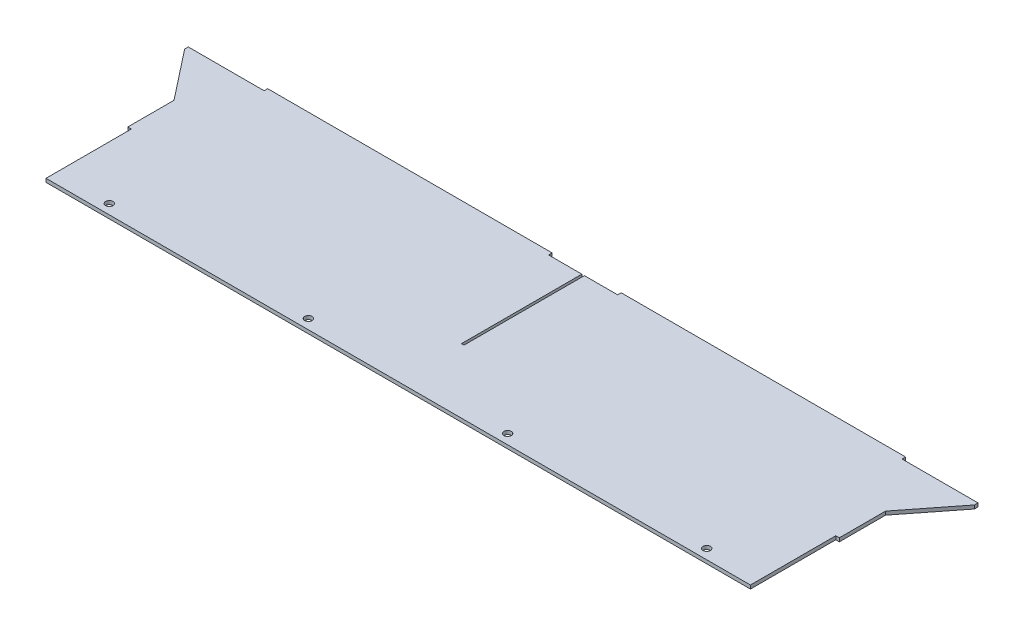
SolidWorks part; units mm, degrees
material "6061-T6 (SS)"
ref_plane "X-Y Datum" through (0, 0, 0) normal (0, 0, 1) x (1, 0, 0)
ref_plane "X-Z Datum" through (0, 0, 0) normal (0, 1, 0) x (1, 0, 0)
ref_plane "Y-Z Datum" through (0, 0, 0) normal (1, 0, 0) x (0, 0, -1)
sketch "Sketch1" plane through (0, 0, 0) normal (0, 1, 0) x (1, 0, 0)
  line L1 (-317.6778, 82.55) -> (317.6778, 82.55)
  line L2 (-317.6778, 82.55) -> (-317.6778, -82.55)
  line L3 (-317.6778, -82.55) -> (317.6778, -82.55)
  line L4 (317.6778, 82.55) -> (317.6778, -82.55)
  line L5 (-317.6778, 82.55) -> (317.6778, -82.55) construction
  line L6 (-317.6778, -82.55) -> (317.6778, 82.55) construction
  point P0 (0, 0)
  dimension "D1" = 635.3556
  dimension "D2" = 165.1
extrude "Boss-Extrude1" add sketch "Sketch1" along normal mid plane 3.175
sketch "Sketch2" plane through (0, 0, -82.55) normal (0, 0, -1) x (-1, 0, 0)
  line L20 (-317.6778, -1.5875) -> (317.6778, -1.5875) construction
  line L21 (-284.8229, -1.5875) -> (-30.8229, -1.5875)
  line L22 (30.8229, -1.5875) -> (284.8229, -1.5875)
  line L40 (30.8229, -1.5875) -> (30.8229, 1.5875)
  line L41 (30.8229, 1.5875) -> (284.8229, 1.5875)
  line L42 (284.8229, 1.5875) -> (284.8229, -1.5875)
  line L56 (-284.8229, -1.5875) -> (-284.8229, 1.5875)
  line L57 (-284.8229, 1.5875) -> (-30.8229, 1.5875)
  line L58 (-30.8229, 1.5875) -> (-30.8229, -1.5875)
extrude "Boss-Extrude2" add sketch "Sketch2" along normal blind 3.175
sketch "Sketch3" plane through (0, -1.5875, 0) normal (0, -1, 0) x (1, 0, 0)
  line L0 (317.6778, -82.55) -> (352.6028, -82.55)
  line L1 (352.6028, -82.55) -> (352.6028, -79.375)
  line L3 (352.6028, -79.375) -> (317.6778, -34.925)
  line L4 (317.6778, 82.55) -> (317.6778, -82.55) construction
  line L17 (317.6778, -82.55) -> (317.6778, 82.55)
  line L18 (317.6778, 82.55) -> (-317.6778, 82.55)
  line L19 (-317.6778, 82.55) -> (-317.6778, -82.55)
  line L20 (-317.6778, -82.55) -> (-284.8229, -82.55)
  line L21 (-284.8229, -82.55) -> (-284.8229, -85.725)
  line L22 (-284.8229, -85.725) -> (-30.8229, -85.725)
  line L23 (-30.8229, -85.725) -> (-30.8229, -82.55)
  line L24 (-30.8229, -82.55) -> (30.8229, -82.55)
  line L25 (30.8229, -82.55) -> (30.8229, -85.725)
  line L26 (30.8229, -85.725) -> (284.8229, -85.725)
  line L27 (284.8229, -85.725) -> (284.8229, -82.55)
  line L28 (284.8229, -82.55) -> (317.6778, -82.55)
  line L29 (317.6778, -82.55) -> (317.6778, -34.925)
  dimension "D1" = 34.925
  dimension "D2" = 3.175
  dimension "D3" = 44.45
  dimension "D4" = 0
extrude "Boss-Extrude3" add sketch "Sketch3" against normal blind 3.175
mirror "Mirror1" about plane through (0, 0, 0) normal (1, 0, 0) of "Boss-Extrude3"
sketch "Sketch4" plane through (0, -1.5875, 0) normal (0, -1, 0) x (1, 0, 0)
  line L0 (-284.4038, 82.55) -> (-284.4038, 71.882)
  line L1 (-317.6778, 82.55) -> (317.6778, 82.55) construction
  line L2 (-284.4038, 71.882) -> (-317.6778, 71.882)
  line L3 (-317.6778, -34.925) -> (-317.6778, 82.55) construction
  circle A0 centre (-284.4038, 71.882) radius 3.675
extrude "Cut-Extrude1" [suppressed] cut sketch "Sketch4" against normal through all contours L2 A0 L0 | L0 A0 L2
pattern_linear "LPattern1" [suppressed] count 5 spacing 139.7 of bodies 107
sketch "Sketch5" plane through (0, -1.5875, 0) normal (0, -1, 0) x (1, 0, 0)
  line L0 (-317.6778, 82.55) -> (317.6778, 82.55) construction
  line L1 (-317.6778, -34.925) -> (-317.6778, 82.55) construction
  line L2 (-317.6778, 82.55) -> (317.6778, 82.55)
  line L3 (-317.6778, -34.925) -> (-317.6778, 82.55)
  line L4 (0, 127.4245) -> (0, -127.4245) construction
  line L5 (-317.6778, 82.55) -> (-314.5028, 82.55)
  line L6 (-317.6778, 82.55) -> (-317.6778, 6.35)
  line L7 (-317.6778, 6.35) -> (-314.5028, 6.35)
  line L8 (-314.5028, 82.55) -> (-314.5028, 6.35)
  line L9 (317.6778, 6.35) -> (314.5028, 6.35)
  line L10 (314.5028, 82.55) -> (314.5028, 6.35)
  line L11 (317.6778, -34.925) -> (317.6778, 82.55)
  line L12 (30.8229, -82.55) -> (-30.8229, -82.55) construction
  line L13 (30.8229, -82.55) -> (-30.8229, -82.55)
  line L14 (-1.143, -85.725) -> (-1.143, -82.55) construction
  line L15 (-1.143, -85.725) -> (-1.143, -82.55)
  line L17 (-1.143, -82.55) -> (1.143, -82.55)
  line L18 (-1.143, -82.55) -> (-1.143, 24.892)
  line L19 (-1.143, 24.892) -> (1.143, 24.892)
  line L20 (1.143, -82.55) -> (1.143, 24.892)
  point P10 (0, 0)
  line M10 (317.6778, -34.925) -> (317.6778, 82.55)
  line M11 (317.6778, 82.55) -> (-317.6778, 82.55)
  line M12 (-317.6778, 82.55) -> (-317.6778, -34.925)
  dimension "D1" = 3.175
  dimension "D2" = 76.2
  dimension "D3" = 2.286
  dimension "D4" = 107.442
extrude "Cut-Extrude2" cut sketch "Sketch5" against normal through all contours L19 L4 L17 L20 | L4 L19 L18 L13 | L8 L2 L7 M12 | L10 L9 M11 M10 region at (316.0903, -1.5875, 44.45) region at (0.5715, -1.5875, -28.829) region at (-0.5715, -1.5875, -28.829) region at (-316.0903, -1.5875, 44.45)
sketch "Sketch6" plane through (0, -1.5875, 0) normal (0, -1, 0) x (1, 0, 0)
  line L0 (-314.5028, 82.55) -> (314.5028, 82.55) construction
  line L1 (-314.5028, 82.55) -> (314.5028, 82.55)
  line L2 (0, 127.6954) -> (0, 37.4046) construction
  line L3 (314.5028, 82.55) -> (314.5028, 6.35) construction
  circle A0 centre (266.7, 73.8124) radius 3
  point P6 (0, 82.55)
  dimension "D1" = 6
  dimension "D2" = 8.7376
  dimension "D3" = 47.8028
hole_wizard "M6 Clearance Hole1" positions "Sketch7" profile "Sketch8" hole size "M6" standard "ANSI Metric" end condition through all
sketch "Sketch7" plane through (0, 1.5875, 0) normal (0, 1, 0) x (1, 0, 0)
  point P0 (266.7, -73.8124)
sketch "Sketch8" plane through (266.7, 1.5875, 73.8124) normal (1, 0, 0) x (0, 0, 1)
  line L0 (0, 0) -> (0, 3.175)
  line L1 (0, 3.175) -> (3.3, 3.175)
  line L2 (3.3, 3.175) -> (3.3, 0)
  line L5 (3.3, 0) -> (0, 0)
  line L11 (0, -6.35) -> (0, 107.95) construction
  dimension "Thru Hole Dia." = 6.6
  dimension "Thru Hole Depth" = 3.175
pattern_linear "LPattern2" count 4 spacing 177.8 along (-1, 0, 0) of "M6 Clearance Hole1"
